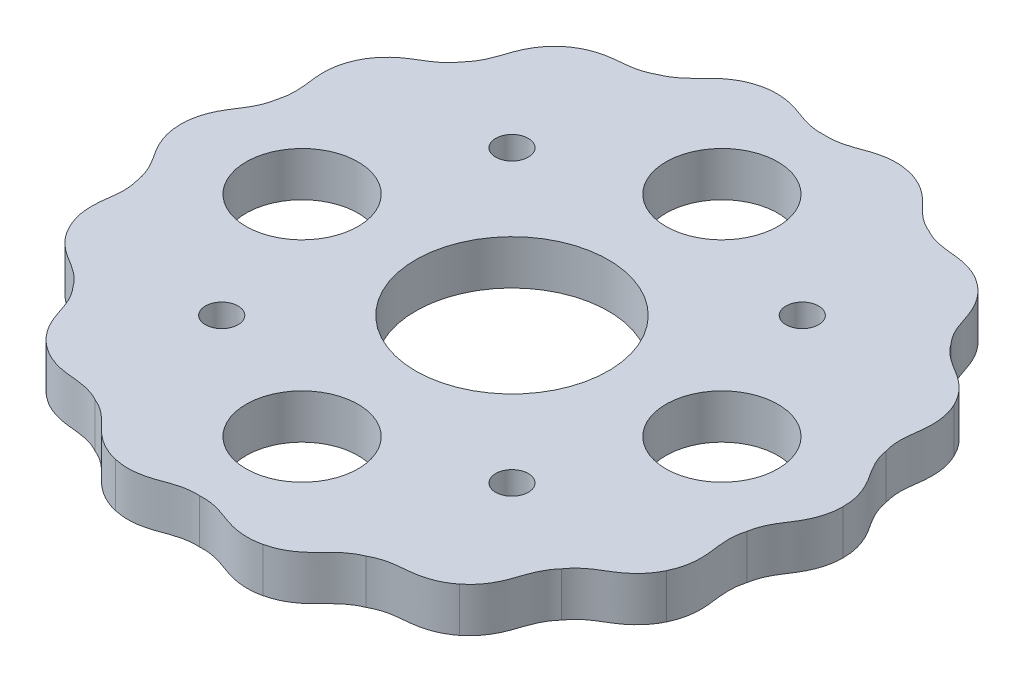
SolidWorks part; units mm, degrees
ref_plane "Front Plane" through (0, 0, 0) normal (0, 0, 1) x (1, 0, 0)
ref_plane "Top Plane" through (0, 0, 0) normal (0, 1, 0) x (1, 0, 0)
ref_plane "Right Plane" through (0, 0, 0) normal (1, 0, 0) x (0, 0, -1)
sketch "Sketch1" plane through (0, 0, 0) normal (0, 1, 0) x (1, 0, 0)
  line L0 (0, 0) -> (37.5, 0) construction
  line L1 (0, 0) -> (37.4807, 1.2019) construction
  line L2 (0, 0) -> (37.423, 2.4026) construction
  line L3 (0, 0) -> (37.3267, 3.6009) construction
  line L4 (0, 0) -> (37.1921, 4.7954) construction
  line L5 (0, 0) -> (37.0193, 5.985) construction
  line L6 (0, 0) -> (36.8085, 7.1684) construction
  line L7 (0, 0) -> (36.5598, 8.3445) construction
  line L8 (0, 0) -> (36.2736, 9.512) construction
  line L9 (0, 0) -> (35.95, 10.6698) construction
  line L10 (0, 0) -> (35.5896, 11.8166) construction
  line L11 (0, 0) -> (35.1926, 12.9512) construction
  line L12 (0, 0) -> (34.7594, 14.0725) construction
  line L13 (0, 0) -> (34.2905, 15.1794) construction
  line L14 (0, 0) -> (33.7863, 16.2706) construction
  line L15 (37.5, 0) -> (38.5, 0) construction
  line L16 (37.4807, 1.2019) -> (38.3521, 1.6927) construction
  line L17 (37.423, 2.4026) -> (37.9413, 3.2578) construction
  line L18 (37.3267, 3.6009) -> (37.3588, 4.6003) construction
  line L19 (37.1921, 4.7954) -> (36.7296, 5.682) construction
  line L20 (37.0193, 5.985) -> (36.1812, 6.5305) construction
  line L21 (36.8085, 7.1684) -> (35.8105, 7.2325) construction
  line L22 (36.5598, 8.3445) -> (35.5849, 8.122) construction
  line L23 (37, 0.0019) -> (37, 0)
  line L24 (33.3367, 16.052) -> (33.3358, 16.0537)
  line L25 (37, -0.0019) -> (37, 0)
  line L26 (33.3367, -16.052) -> (33.3358, -16.0537)
  line L27 (33.335, -16.0554) -> (33.3358, -16.0537)
  line L28 (23.0706, -28.9266) -> (23.0691, -28.9278)
  line L29 (23.0677, -28.9289) -> (23.0691, -28.9278)
  line L30 (8.2351, -36.0719) -> (8.2333, -36.0723)
  line L31 (8.2315, -36.0727) -> (8.2333, -36.0723)
  line L32 (-8.2315, -36.0727) -> (-8.2333, -36.0723)
  line L33 (-8.2351, -36.0719) -> (-8.2333, -36.0723)
  line L34 (-23.0677, -28.9289) -> (-23.0691, -28.9278)
  line L35 (-23.0706, -28.9266) -> (-23.0691, -28.9278)
  line L36 (-33.335, -16.0554) -> (-33.3358, -16.0537)
  line L37 (-33.3367, -16.052) -> (-33.3358, -16.0537)
  line L38 (-37, -0.0019) -> (-37, 0)
  line L39 (-37, 0.0019) -> (-37, 0)
  line L40 (-33.3367, 16.052) -> (-33.3358, 16.0537)
  line L41 (-33.335, 16.0554) -> (-33.3358, 16.0537)
  line L42 (-23.0706, 28.9266) -> (-23.0691, 28.9278)
  line L43 (-23.0677, 28.9289) -> (-23.0691, 28.9278)
  line L44 (-8.2351, 36.0719) -> (-8.2333, 36.0723)
  line L45 (-8.2315, 36.0727) -> (-8.2333, 36.0723)
  line L46 (8.2315, 36.0727) -> (8.2333, 36.0723)
  line L47 (8.2351, 36.0719) -> (8.2333, 36.0723)
  line L48 (23.0677, 28.9289) -> (23.0691, 28.9278)
  line L49 (23.0706, 28.9266) -> (23.0691, 28.9278)
  line L50 (33.335, 16.0554) -> (33.3358, 16.0537)
  line L51 (35.5, 0.0037) -> (35.5, 0)
  line L52 (31.986, 15.3995) -> (31.9844, 15.4029)
  line L53 (35.5, -0.0037) -> (35.5, 0)
  line L54 (31.986, -15.3995) -> (31.9844, -15.4029)
  line L55 (31.9828, -15.4062) -> (31.9844, -15.4029)
  line L56 (22.1368, -27.7527) -> (22.1339, -27.755)
  line L57 (22.131, -27.7573) -> (22.1339, -27.755)
  line L58 (7.9031, -34.6091) -> (7.8995, -34.6099)
  line L59 (7.8959, -34.6108) -> (7.8995, -34.6099)
  line L60 (-7.8959, -34.6108) -> (-7.8995, -34.6099)
  line L61 (-7.9031, -34.6091) -> (-7.8995, -34.6099)
  line L62 (-22.131, -27.7573) -> (-22.1339, -27.755)
  line L63 (-22.1368, -27.7527) -> (-22.1339, -27.755)
  line L64 (-31.9828, -15.4062) -> (-31.9844, -15.4029)
  line L65 (-31.986, -15.3995) -> (-31.9844, -15.4029)
  line L66 (-35.5, -0.0037) -> (-35.5, 0)
  line L67 (-35.5, 0.0037) -> (-35.5, 0)
  line L68 (-31.986, 15.3995) -> (-31.9844, 15.4029)
  line L69 (-31.9828, 15.4062) -> (-31.9844, 15.4029)
  line L70 (-22.1368, 27.7527) -> (-22.1339, 27.755)
  line L71 (-22.131, 27.7573) -> (-22.1339, 27.755)
  line L72 (-7.9031, 34.6091) -> (-7.8995, 34.6099)
  line L73 (-7.8959, 34.6108) -> (-7.8995, 34.6099)
  line L74 (7.8959, 34.6108) -> (7.8995, 34.6099)
  line L75 (7.9031, 34.6091) -> (7.8995, 34.6099)
  line L76 (22.131, 27.7573) -> (22.1339, 27.755)
  line L77 (22.1368, 27.7527) -> (22.1339, 27.755)
  line L78 (31.9828, 15.4062) -> (31.9844, 15.4029)
  circle A0 centre (0, 0) radius 35 construction
  circle A1 centre (37.5, 0) radius 2.5 construction
  circle A2 centre (0, 0) radius 37.5 construction
  spline S0 degree 3 poles (35.5849, 8.122) (35.6266, 7.5364) (36.0345, 6.7125) (36.7836, 5.6218) (37.4152, 4.5501) (38.2239, 2.702) (38.5014, 1.1074) (38.5, 0) knots 0 0 0 0 0.195516 0.310928 0.453873 0.621058 1 1 1 1
  spline S1 degree 3 poles (35.5849, 8.122) (35.3683, 8.6678) (35.3784, 9.5871) (35.5801, 10.8948) (35.6841, 12.1344) (35.611, 14.1503) (35.169, 15.7074) (34.6873, 16.7045) knots 0 0 0 0 0.195516 0.310928 0.453873 0.621058 1 1 1 1
  spline S2 degree 1 poles (34.1119, 7.7858) (33.3367, 16.052) knots 0 0 1 1 construction
  spline S3 degree 1 poles (34.1119, 7.7858) (37, 0.0019) knots 0 0 1 1 construction
  spline S4 degree 3 poles (33.3367, 16.052) (33.6005, 15.5058) (33.9037, 14.6401) (34.1146, 13.4372) (34.174, 12.5211) (34.1413, 11.5771) (34.0239, 10.6392) (33.8823, 9.6155) (33.9055, 8.625) (34.0243, 8.0514) (34.1119, 7.7858) knots 0.015853 0.015853 0.015853 0.015853 0.26189 0.384908 0.507927 0.630945 0.753963 0.876982 0.938491 1 1 1 1
  spline S5 degree 3 poles (34.1119, 7.7858) (34.1483, 7.5085) (34.2901, 6.9402) (34.6989, 6.0377) (35.2706, 5.1769) (35.7834, 4.3828) (36.2224, 3.5464) (36.5664, 2.6953) (36.8983, 1.52) (37.0008, 0.6085) (37, 0.0019) knots 0.015853 0.015853 0.015853 0.015853 0.077362 0.138872 0.26189 0.384908 0.507927 0.630945 0.753963 1 1 1 1
  spline S6 degree 3 poles (37, -0.0019) (37.0008, -0.6085) (36.8983, -1.52) (36.5664, -2.6953) (36.2224, -3.5464) (35.7834, -4.3828) (35.2706, -5.1769) (34.6989, -6.0377) (34.2901, -6.9402) (34.1483, -7.5085) (34.1119, -7.7858) knots 0.015853 0.015853 0.015853 0.015853 0.26189 0.384908 0.507927 0.630945 0.753963 0.876982 0.938491 1 1 1 1
  spline S7 degree 3 poles (34.1119, -7.7858) (34.0243, -8.0514) (33.9055, -8.625) (33.8823, -9.6155) (34.0239, -10.6392) (34.1413, -11.5771) (34.174, -12.5211) (34.1146, -13.4372) (33.9037, -14.6401) (33.6005, -15.5058) (33.3367, -16.052) knots 0.015853 0.015853 0.015853 0.015853 0.077362 0.138872 0.26189 0.384908 0.507927 0.630945 0.753963 1 1 1 1
  spline S8 degree 3 poles (33.335, -16.0554) (33.0725, -16.6022) (32.5847, -17.3791) (31.7758, -18.2939) (31.0965, -18.9115) (30.3381, -19.4746) (29.5316, -19.9675) (28.6429, -20.4951) (27.8831, -21.1308) (27.5087, -21.5813) (27.3556, -21.8154) knots 0.015853 0.015853 0.015853 0.015853 0.26189 0.384908 0.507927 0.630945 0.753963 0.876982 0.938491 1 1 1 1
  spline S9 degree 3 poles (27.3556, -21.8154) (27.1615, -22.0167) (26.8056, -22.4819) (26.3549, -23.3642) (26.0383, -24.348) (25.7371, -25.2439) (25.357, -26.1087) (24.906, -26.9083) (24.1941, -27.9005) (23.5453, -28.549) (23.0706, -28.9266) knots 0.015853 0.015853 0.015853 0.015853 0.077362 0.138872 0.26189 0.384908 0.507927 0.630945 0.753963 1 1 1 1
  spline S10 degree 3 poles (23.0677, -28.9289) (22.5939, -29.3077) (21.8173, -29.796) (20.6915, -30.2693) (19.8116, -30.531) (18.884, -30.7092) (17.9435, -30.8034) (16.9139, -30.8931) (15.9535, -31.1362) (15.4207, -31.3797) (15.1812, -31.5241) knots 0.015853 0.015853 0.015853 0.015853 0.26189 0.384908 0.507927 0.630945 0.753963 0.876982 0.938491 1 1 1 1
  spline S11 degree 3 poles (15.1812, -31.5241) (14.919, -31.6213) (14.3964, -31.886) (13.6076, -32.4854) (12.8955, -33.2344) (12.2354, -33.9109) (11.5177, -34.5251) (10.7645, -35.0499) (9.6926, -35.6349) (8.8266, -35.9377) (8.2351, -36.0719) knots 0.015853 0.015853 0.015853 0.015853 0.077362 0.138872 0.26189 0.384908 0.507927 0.630945 0.753963 1 1 1 1
  spline S12 degree 3 poles (8.2315, -36.0727) (7.6402, -36.2085) (6.7287, -36.3114) (5.5091, -36.2494) (4.6028, -36.1034) (3.6897, -35.8614) (2.8014, -35.5383) (1.8349, -35.1724) (0.8641, -34.9747) (0.2785, -34.9629) (0, -34.9891) knots 0.015853 0.015853 0.015853 0.015853 0.26189 0.384908 0.507927 0.630945 0.753963 0.876982 0.938491 1 1 1 1
  spline S13 degree 3 poles (0, -34.9891) (-0.2785, -34.9629) (-0.8641, -34.9747) (-1.8349, -35.1724) (-2.8014, -35.5383) (-3.6897, -35.8614) (-4.6028, -36.1034) (-5.5091, -36.2494) (-6.7287, -36.3114) (-7.6402, -36.2085) (-8.2315, -36.0727) knots 0.015853 0.015853 0.015853 0.015853 0.077362 0.138872 0.26189 0.384908 0.507927 0.630945 0.753963 1 1 1 1
  spline S14 degree 3 poles (-8.2351, -36.0719) (-8.8266, -35.9377) (-9.6926, -35.6349) (-10.7645, -35.0499) (-11.5177, -34.5251) (-12.2354, -33.9109) (-12.8955, -33.2344) (-13.6076, -32.4854) (-14.3964, -31.886) (-14.919, -31.6213) (-15.1812, -31.5241) knots 0.015853 0.015853 0.015853 0.015853 0.26189 0.384908 0.507927 0.630945 0.753963 0.876982 0.938491 1 1 1 1
  spline S15 degree 3 poles (-15.1812, -31.5241) (-15.4207, -31.3797) (-15.9535, -31.1362) (-16.9139, -30.8931) (-17.9435, -30.8034) (-18.884, -30.7092) (-19.8116, -30.531) (-20.6915, -30.2693) (-21.8173, -29.796) (-22.5939, -29.3077) (-23.0677, -28.9289) knots 0.015853 0.015853 0.015853 0.015853 0.077362 0.138872 0.26189 0.384908 0.507927 0.630945 0.753963 1 1 1 1
  spline S16 degree 3 poles (-23.0706, -28.9266) (-23.5453, -28.549) (-24.1941, -27.9005) (-24.906, -26.9083) (-25.357, -26.1087) (-25.7371, -25.2439) (-26.0383, -24.348) (-26.3549, -23.3642) (-26.8056, -22.4819) (-27.1615, -22.0167) (-27.3556, -21.8154) knots 0.015853 0.015853 0.015853 0.015853 0.26189 0.384908 0.507927 0.630945 0.753963 0.876982 0.938491 1 1 1 1
  spline S17 degree 3 poles (-27.3556, -21.8154) (-27.5087, -21.5813) (-27.8831, -21.1308) (-28.6429, -20.4951) (-29.5316, -19.9675) (-30.3381, -19.4746) (-31.0965, -18.9115) (-31.7758, -18.2939) (-32.5847, -17.3791) (-33.0725, -16.6022) (-33.335, -16.0554) knots 0.015853 0.015853 0.015853 0.015853 0.077362 0.138872 0.26189 0.384908 0.507927 0.630945 0.753963 1 1 1 1
  spline S18 degree 3 poles (-33.3367, -16.052) (-33.6005, -15.5058) (-33.9037, -14.6401) (-34.1146, -13.4372) (-34.174, -12.5211) (-34.1413, -11.5771) (-34.0239, -10.6392) (-33.8823, -9.6155) (-33.9055, -8.625) (-34.0243, -8.0514) (-34.1119, -7.7858) knots 0.015853 0.015853 0.015853 0.015853 0.26189 0.384908 0.507927 0.630945 0.753963 0.876982 0.938491 1 1 1 1
  spline S19 degree 3 poles (-34.1119, -7.7858) (-34.1483, -7.5085) (-34.2901, -6.9402) (-34.6989, -6.0377) (-35.2706, -5.1769) (-35.7834, -4.3828) (-36.2224, -3.5464) (-36.5664, -2.6953) (-36.8983, -1.52) (-37.0008, -0.6085) (-37, -0.0019) knots 0.015853 0.015853 0.015853 0.015853 0.077362 0.138872 0.26189 0.384908 0.507927 0.630945 0.753963 1 1 1 1
  spline S20 degree 3 poles (-37, 0.0019) (-37.0008, 0.6085) (-36.8983, 1.52) (-36.5664, 2.6953) (-36.2224, 3.5464) (-35.7834, 4.3828) (-35.2706, 5.1769) (-34.6989, 6.0377) (-34.2901, 6.9402) (-34.1483, 7.5085) (-34.1119, 7.7858) knots 0.015853 0.015853 0.015853 0.015853 0.26189 0.384908 0.507927 0.630945 0.753963 0.876982 0.938491 1 1 1 1
  spline S21 degree 3 poles (-34.1119, 7.7858) (-34.0243, 8.0514) (-33.9055, 8.625) (-33.8823, 9.6155) (-34.0239, 10.6392) (-34.1413, 11.5771) (-34.174, 12.5211) (-34.1146, 13.4372) (-33.9037, 14.6401) (-33.6005, 15.5058) (-33.3367, 16.052) knots 0.015853 0.015853 0.015853 0.015853 0.077362 0.138872 0.26189 0.384908 0.507927 0.630945 0.753963 1 1 1 1
  spline S22 degree 3 poles (-33.335, 16.0554) (-33.0725, 16.6022) (-32.5847, 17.3791) (-31.7758, 18.2939) (-31.0965, 18.9115) (-30.3381, 19.4746) (-29.5316, 19.9675) (-28.6429, 20.4951) (-27.8831, 21.1308) (-27.5087, 21.5813) (-27.3556, 21.8154) knots 0.015853 0.015853 0.015853 0.015853 0.26189 0.384908 0.507927 0.630945 0.753963 0.876982 0.938491 1 1 1 1
  spline S23 degree 3 poles (-27.3556, 21.8154) (-27.1615, 22.0167) (-26.8056, 22.4819) (-26.3549, 23.3642) (-26.0383, 24.348) (-25.7371, 25.2439) (-25.357, 26.1087) (-24.906, 26.9083) (-24.1941, 27.9005) (-23.5453, 28.549) (-23.0706, 28.9266) knots 0.015853 0.015853 0.015853 0.015853 0.077362 0.138872 0.26189 0.384908 0.507927 0.630945 0.753963 1 1 1 1
  spline S24 degree 3 poles (-23.0677, 28.9289) (-22.5939, 29.3077) (-21.8173, 29.796) (-20.6915, 30.2693) (-19.8116, 30.531) (-18.884, 30.7092) (-17.9435, 30.8034) (-16.9139, 30.8931) (-15.9535, 31.1362) (-15.4207, 31.3797) (-15.1812, 31.5241) knots 0.015853 0.015853 0.015853 0.015853 0.26189 0.384908 0.507927 0.630945 0.753963 0.876982 0.938491 1 1 1 1
  spline S25 degree 3 poles (-15.1812, 31.5241) (-14.919, 31.6213) (-14.3964, 31.886) (-13.6076, 32.4854) (-12.8955, 33.2344) (-12.2354, 33.9109) (-11.5177, 34.5251) (-10.7645, 35.0499) (-9.6926, 35.6349) (-8.8266, 35.9377) (-8.2351, 36.0719) knots 0.015853 0.015853 0.015853 0.015853 0.077362 0.138872 0.26189 0.384908 0.507927 0.630945 0.753963 1 1 1 1
  spline S26 degree 3 poles (-8.2315, 36.0727) (-7.6402, 36.2085) (-6.7287, 36.3114) (-5.5091, 36.2494) (-4.6028, 36.1034) (-3.6897, 35.8614) (-2.8014, 35.5383) (-1.8349, 35.1724) (-0.8641, 34.9747) (-0.2785, 34.9629) (0, 34.9891) knots 0.015853 0.015853 0.015853 0.015853 0.26189 0.384908 0.507927 0.630945 0.753963 0.876982 0.938491 1 1 1 1
  spline S27 degree 3 poles (0, 34.9891) (0.2785, 34.9629) (0.8641, 34.9747) (1.8349, 35.1724) (2.8014, 35.5383) (3.6897, 35.8614) (4.6028, 36.1034) (5.5091, 36.2494) (6.7287, 36.3114) (7.6402, 36.2085) (8.2315, 36.0727) knots 0.015853 0.015853 0.015853 0.015853 0.077362 0.138872 0.26189 0.384908 0.507927 0.630945 0.753963 1 1 1 1
  spline S28 degree 3 poles (8.2351, 36.0719) (8.8266, 35.9377) (9.6926, 35.6349) (10.7645, 35.0499) (11.5177, 34.5251) (12.2354, 33.9109) (12.8955, 33.2344) (13.6076, 32.4854) (14.3964, 31.886) (14.919, 31.6213) (15.1812, 31.5241) knots 0.015853 0.015853 0.015853 0.015853 0.26189 0.384908 0.507927 0.630945 0.753963 0.876982 0.938491 1 1 1 1
  spline S29 degree 3 poles (15.1812, 31.5241) (15.4207, 31.3797) (15.9535, 31.1362) (16.9139, 30.8931) (17.9435, 30.8034) (18.884, 30.7092) (19.8116, 30.531) (20.6915, 30.2693) (21.8173, 29.796) (22.5939, 29.3077) (23.0677, 28.9289) knots 0.015853 0.015853 0.015853 0.015853 0.077362 0.138872 0.26189 0.384908 0.507927 0.630945 0.753963 1 1 1 1
  spline S30 degree 3 poles (23.0706, 28.9266) (23.5453, 28.549) (24.1941, 27.9005) (24.906, 26.9083) (25.357, 26.1087) (25.7371, 25.2439) (26.0383, 24.348) (26.3549, 23.3642) (26.8056, 22.4819) (27.1615, 22.0167) (27.3556, 21.8154) knots 0.015853 0.015853 0.015853 0.015853 0.26189 0.384908 0.507927 0.630945 0.753963 0.876982 0.938491 1 1 1 1
  spline S31 degree 3 poles (27.3556, 21.8154) (27.5087, 21.5813) (27.8831, 21.1308) (28.6429, 20.4951) (29.5316, 19.9675) (30.3381, 19.4746) (31.0965, 18.9115) (31.7758, 18.2939) (32.5847, 17.3791) (33.0725, 16.6022) (33.335, 16.0554) knots 0.015853 0.015853 0.015853 0.015853 0.077362 0.138872 0.26189 0.384908 0.507927 0.630945 0.753963 1 1 1 1
  spline S32 degree 1 poles (32.6448, 7.451) (35.5, 0.0037) knots 0 0 1 1 construction
  spline S33 degree 1 poles (32.6448, 7.451) (31.986, 15.3995) knots 0 0 1 1 construction
  spline S34 degree 3 poles (35.5, 0.0037) (35.5006, 0.4959) (35.4183, 1.2336) (35.1496, 2.1927) (34.8707, 2.8896) (34.4997, 3.6015) (34.1394, 4.1652) (33.6939, 4.8394) (33.3068, 5.4873) (32.9751, 6.1975) (32.758, 6.8733) (32.6748, 7.2607) (32.6448, 7.451) knots 0.023011 0.023011 0.023011 0.023011 0.267258 0.389382 0.511505 0.633629 0.755753 0.816814 0.877876 0.938938 0.969469 1 1 1 1
  spline S35 degree 3 poles (32.6448, 7.451) (32.5893, 7.6354) (32.4961, 8.0206) (32.3985, 8.7236) (32.3893, 9.5074) (32.4569, 10.2591) (32.5657, 11.0598) (32.6458, 11.724) (32.6712, 12.5264) (32.6201, 13.2752) (32.446, 14.256) (32.2001, 14.9563) (31.986, 15.3995) knots 0.023011 0.023011 0.023011 0.023011 0.053542 0.084072 0.145134 0.206196 0.267258 0.389382 0.511505 0.633629 0.755753 1 1 1 1
  spline S36 degree 3 poles (32.6448, -7.451) (32.6748, -7.2607) (32.758, -6.8733) (32.9751, -6.1975) (33.3068, -5.4873) (33.6939, -4.8394) (34.1394, -4.1652) (34.4997, -3.6015) (34.8707, -2.8896) (35.1496, -2.1927) (35.4183, -1.2336) (35.5006, -0.4959) (35.5, -0.0037) knots 0.023011 0.023011 0.023011 0.023011 0.053542 0.084072 0.145134 0.206196 0.267258 0.389382 0.511505 0.633629 0.755753 1 1 1 1
  spline S37 degree 3 poles (31.986, -15.3995) (32.2001, -14.9563) (32.446, -14.256) (32.6201, -13.2752) (32.6712, -12.5264) (32.6458, -11.724) (32.5657, -11.0598) (32.4569, -10.2591) (32.3893, -9.5074) (32.3985, -8.7236) (32.4961, -8.0206) (32.5893, -7.6354) (32.6448, -7.451) knots 0.023011 0.023011 0.023011 0.023011 0.267258 0.389382 0.511505 0.633629 0.755753 0.816814 0.877876 0.938938 0.969469 1 1 1 1
  spline S38 degree 3 poles (26.1791, -20.8771) (26.2887, -20.7187) (26.5317, -20.4057) (27.0205, -19.8911) (27.6275, -19.3952) (28.2574, -18.9793) (28.9513, -18.5652) (29.5206, -18.2137) (30.1637, -17.7333) (30.7173, -17.2264) (31.3755, -16.4789) (31.7698, -15.8499) (31.9828, -15.4062) knots 0.023011 0.023011 0.023011 0.023011 0.053542 0.084072 0.145134 0.206196 0.267258 0.389382 0.511505 0.633629 0.755753 1 1 1 1
  spline S39 degree 3 poles (22.1368, -27.7527) (22.522, -27.4463) (23.0474, -26.922) (23.6297, -26.1139) (24.0007, -25.4614) (24.326, -24.7275) (24.542, -24.0943) (24.7914, -23.3257) (25.0566, -22.619) (25.405, -21.9169) (25.798, -21.3258) (26.0491, -21.0192) (26.1791, -20.8771) knots 0.023011 0.023011 0.023011 0.023011 0.267258 0.389382 0.511505 0.633629 0.755753 0.816814 0.877876 0.938938 0.969469 1 1 1 1
  spline S40 degree 3 poles (14.5283, -30.1683) (14.6957, -30.0732) (15.0505, -29.8966) (15.7143, -29.645) (16.4763, -29.4616) (17.2242, -29.3602) (18.0291, -29.2882) (18.6945, -29.2185) (19.4823, -29.0647) (20.201, -28.8482) (21.1184, -28.4603) (21.7465, -28.0647) (22.131, -27.7573) knots 0.023011 0.023011 0.023011 0.023011 0.053542 0.084072 0.145134 0.206196 0.267258 0.389382 0.511505 0.633629 0.755753 1 1 1 1
  spline S41 degree 3 poles (7.9031, -34.6091) (8.3831, -34.5002) (9.084, -34.2557) (9.9593, -33.7804) (10.5766, -33.3534) (11.1881, -32.8334) (11.6575, -32.3566) (12.2156, -31.7723) (12.7612, -31.2507) (13.3797, -30.7693) (13.9903, -30.4072) (14.3495, -30.2399) (14.5283, -30.1683) knots 0.023011 0.023011 0.023011 0.023011 0.267258 0.389382 0.511505 0.633629 0.755753 0.816814 0.877876 0.938938 0.969469 1 1 1 1
  spline S42 degree 3 poles (0, -33.4843) (0.1922, -33.4712) (0.5884, -33.4661) (1.2956, -33.5274) (2.0617, -33.6928) (2.7796, -33.926) (3.536, -34.2103) (4.1657, -34.4362) (4.9423, -34.6394) (5.6838, -34.7562) (6.6786, -34.8048) (7.4161, -34.7209) (7.8959, -34.6108) knots 0.023011 0.023011 0.023011 0.023011 0.053542 0.084072 0.145134 0.206196 0.267258 0.389382 0.511505 0.633629 0.755753 1 1 1 1
  spline S43 degree 3 poles (-7.8959, -34.6108) (-7.4161, -34.7209) (-6.6786, -34.8048) (-5.6838, -34.7562) (-4.9423, -34.6394) (-4.1657, -34.4362) (-3.536, -34.2103) (-2.7796, -33.926) (-2.0617, -33.6928) (-1.2956, -33.5274) (-0.5884, -33.4661) (-0.1922, -33.4712) (0, -33.4843) knots 0.023011 0.023011 0.023011 0.023011 0.267258 0.389382 0.511505 0.633629 0.755753 0.816814 0.877876 0.938938 0.969469 1 1 1 1
  spline S44 degree 3 poles (-14.5283, -30.1683) (-14.3495, -30.2399) (-13.9903, -30.4072) (-13.3797, -30.7693) (-12.7612, -31.2507) (-12.2156, -31.7723) (-11.6575, -32.3566) (-11.1881, -32.8334) (-10.5766, -33.3534) (-9.9593, -33.7804) (-9.084, -34.2557) (-8.3831, -34.5002) (-7.9031, -34.6091) knots 0.023011 0.023011 0.023011 0.023011 0.053542 0.084072 0.145134 0.206196 0.267258 0.389382 0.511505 0.633629 0.755753 1 1 1 1
  spline S45 degree 3 poles (-22.131, -27.7573) (-21.7465, -28.0647) (-21.1184, -28.4603) (-20.201, -28.8482) (-19.4823, -29.0647) (-18.6945, -29.2185) (-18.0291, -29.2882) (-17.2242, -29.3602) (-16.4763, -29.4616) (-15.7143, -29.645) (-15.0505, -29.8966) (-14.6957, -30.0732) (-14.5283, -30.1683) knots 0.023011 0.023011 0.023011 0.023011 0.267258 0.389382 0.511505 0.633629 0.755753 0.816814 0.877876 0.938938 0.969469 1 1 1 1
  spline S46 degree 3 poles (-26.1791, -20.8771) (-26.0491, -21.0192) (-25.798, -21.3258) (-25.405, -21.9169) (-25.0566, -22.619) (-24.7914, -23.3257) (-24.542, -24.0943) (-24.326, -24.7275) (-24.0007, -25.4614) (-23.6297, -26.1139) (-23.0474, -26.922) (-22.522, -27.4463) (-22.1368, -27.7527) knots 0.023011 0.023011 0.023011 0.023011 0.053542 0.084072 0.145134 0.206196 0.267258 0.389382 0.511505 0.633629 0.755753 1 1 1 1
  spline S47 degree 3 poles (-31.9828, -15.4062) (-31.7698, -15.8499) (-31.3755, -16.4789) (-30.7173, -17.2264) (-30.1637, -17.7333) (-29.5206, -18.2137) (-28.9513, -18.5652) (-28.2574, -18.9793) (-27.6275, -19.3952) (-27.0205, -19.8911) (-26.5317, -20.4057) (-26.2887, -20.7187) (-26.1791, -20.8771) knots 0.023011 0.023011 0.023011 0.023011 0.267258 0.389382 0.511505 0.633629 0.755753 0.816814 0.877876 0.938938 0.969469 1 1 1 1
  spline S48 degree 3 poles (-32.6448, -7.451) (-32.5893, -7.6354) (-32.4961, -8.0206) (-32.3985, -8.7236) (-32.3893, -9.5074) (-32.4569, -10.2591) (-32.5657, -11.0598) (-32.6458, -11.724) (-32.6712, -12.5264) (-32.6201, -13.2752) (-32.446, -14.256) (-32.2001, -14.9563) (-31.986, -15.3995) knots 0.023011 0.023011 0.023011 0.023011 0.053542 0.084072 0.145134 0.206196 0.267258 0.389382 0.511505 0.633629 0.755753 1 1 1 1
  spline S49 degree 3 poles (-35.5, -0.0037) (-35.5006, -0.4959) (-35.4183, -1.2336) (-35.1496, -2.1927) (-34.8707, -2.8896) (-34.4997, -3.6015) (-34.1394, -4.1652) (-33.6939, -4.8394) (-33.3068, -5.4873) (-32.9751, -6.1975) (-32.758, -6.8733) (-32.6748, -7.2607) (-32.6448, -7.451) knots 0.023011 0.023011 0.023011 0.023011 0.267258 0.389382 0.511505 0.633629 0.755753 0.816814 0.877876 0.938938 0.969469 1 1 1 1
  spline S50 degree 3 poles (-32.6448, 7.451) (-32.6748, 7.2607) (-32.758, 6.8733) (-32.9751, 6.1975) (-33.3068, 5.4873) (-33.6939, 4.8394) (-34.1394, 4.1652) (-34.4997, 3.6015) (-34.8707, 2.8896) (-35.1496, 2.1927) (-35.4183, 1.2336) (-35.5006, 0.4959) (-35.5, 0.0037) knots 0.023011 0.023011 0.023011 0.023011 0.053542 0.084072 0.145134 0.206196 0.267258 0.389382 0.511505 0.633629 0.755753 1 1 1 1
  spline S51 degree 3 poles (-31.986, 15.3995) (-32.2001, 14.9563) (-32.446, 14.256) (-32.6201, 13.2752) (-32.6712, 12.5264) (-32.6458, 11.724) (-32.5657, 11.0598) (-32.4569, 10.2591) (-32.3893, 9.5074) (-32.3985, 8.7236) (-32.4961, 8.0206) (-32.5893, 7.6354) (-32.6448, 7.451) knots 0.023011 0.023011 0.023011 0.023011 0.267258 0.389382 0.511505 0.633629 0.755753 0.816814 0.877876 0.938938 0.969469 1 1 1 1
  spline S52 degree 3 poles (-26.1791, 20.8771) (-26.2887, 20.7187) (-26.5317, 20.4057) (-27.0205, 19.8911) (-27.6275, 19.3952) (-28.2574, 18.9793) (-28.9513, 18.5652) (-29.5206, 18.2137) (-30.1637, 17.7333) (-30.7173, 17.2264) (-31.3755, 16.4789) (-31.7698, 15.8499) (-31.9828, 15.4062) knots 0.023011 0.023011 0.023011 0.023011 0.053542 0.084072 0.145134 0.206196 0.267258 0.389382 0.511505 0.633629 0.755753 1 1 1 1
  spline S53 degree 3 poles (-22.1368, 27.7527) (-22.522, 27.4463) (-23.0474, 26.922) (-23.6297, 26.1139) (-24.0007, 25.4614) (-24.326, 24.7275) (-24.542, 24.0943) (-24.7914, 23.3257) (-25.0566, 22.619) (-25.405, 21.9169) (-25.798, 21.3258) (-26.0491, 21.0192) (-26.1791, 20.8771) knots 0.023011 0.023011 0.023011 0.023011 0.267258 0.389382 0.511505 0.633629 0.755753 0.816814 0.877876 0.938938 0.969469 1 1 1 1
  spline S54 degree 3 poles (-14.5283, 30.1683) (-14.6957, 30.0732) (-15.0505, 29.8966) (-15.7143, 29.645) (-16.4763, 29.4616) (-17.2242, 29.3602) (-18.0291, 29.2882) (-18.6945, 29.2185) (-19.4823, 29.0647) (-20.201, 28.8482) (-21.1184, 28.4603) (-21.7465, 28.0647) (-22.131, 27.7573) knots 0.023011 0.023011 0.023011 0.023011 0.053542 0.084072 0.145134 0.206196 0.267258 0.389382 0.511505 0.633629 0.755753 1 1 1 1
  spline S55 degree 3 poles (-7.9031, 34.6091) (-8.3831, 34.5002) (-9.084, 34.2557) (-9.9593, 33.7804) (-10.5766, 33.3534) (-11.1881, 32.8334) (-11.6575, 32.3566) (-12.2156, 31.7723) (-12.7612, 31.2507) (-13.3797, 30.7693) (-13.9903, 30.4072) (-14.3495, 30.2399) (-14.5283, 30.1683) knots 0.023011 0.023011 0.023011 0.023011 0.267258 0.389382 0.511505 0.633629 0.755753 0.816814 0.877876 0.938938 0.969469 1 1 1 1
  spline S56 degree 3 poles (0, 33.4843) (-0.1922, 33.4712) (-0.5884, 33.4661) (-1.2956, 33.5274) (-2.0617, 33.6928) (-2.7796, 33.926) (-3.536, 34.2103) (-4.1657, 34.4362) (-4.9423, 34.6394) (-5.6838, 34.7562) (-6.6786, 34.8048) (-7.4161, 34.7209) (-7.8959, 34.6108) knots 0.023011 0.023011 0.023011 0.023011 0.053542 0.084072 0.145134 0.206196 0.267258 0.389382 0.511505 0.633629 0.755753 1 1 1 1
  spline S57 degree 3 poles (7.8959, 34.6108) (7.4161, 34.7209) (6.6786, 34.8048) (5.6838, 34.7562) (4.9423, 34.6394) (4.1657, 34.4362) (3.536, 34.2103) (2.7796, 33.926) (2.0617, 33.6928) (1.2956, 33.5274) (0.5884, 33.4661) (0.1922, 33.4712) (0, 33.4843) knots 0.023011 0.023011 0.023011 0.023011 0.267258 0.389382 0.511505 0.633629 0.755753 0.816814 0.877876 0.938938 0.969469 1 1 1 1
  spline S58 degree 3 poles (14.5283, 30.1683) (14.3495, 30.2399) (13.9903, 30.4072) (13.3797, 30.7693) (12.7612, 31.2507) (12.2156, 31.7723) (11.6575, 32.3566) (11.1881, 32.8334) (10.5766, 33.3534) (9.9593, 33.7804) (9.084, 34.2557) (8.3831, 34.5002) (7.9031, 34.6091) knots 0.023011 0.023011 0.023011 0.023011 0.053542 0.084072 0.145134 0.206196 0.267258 0.389382 0.511505 0.633629 0.755753 1 1 1 1
  spline S59 degree 3 poles (22.131, 27.7573) (21.7465, 28.0647) (21.1184, 28.4603) (20.201, 28.8482) (19.4823, 29.0647) (18.6945, 29.2185) (18.0291, 29.2882) (17.2242, 29.3602) (16.4763, 29.4616) (15.7143, 29.645) (15.0505, 29.8966) (14.6957, 30.0732) (14.5283, 30.1683) knots 0.023011 0.023011 0.023011 0.023011 0.267258 0.389382 0.511505 0.633629 0.755753 0.816814 0.877876 0.938938 0.969469 1 1 1 1
  spline S60 degree 3 poles (26.1791, 20.8771) (26.0491, 21.0192) (25.798, 21.3258) (25.405, 21.9169) (25.0566, 22.619) (24.7914, 23.3257) (24.542, 24.0943) (24.326, 24.7275) (24.0007, 25.4614) (23.6297, 26.1139) (23.0474, 26.922) (22.522, 27.4463) (22.1368, 27.7527) knots 0.023011 0.023011 0.023011 0.023011 0.053542 0.084072 0.145134 0.206196 0.267258 0.389382 0.511505 0.633629 0.755753 1 1 1 1
  spline S61 degree 3 poles (31.9828, 15.4062) (31.7698, 15.8499) (31.3755, 16.4789) (30.7173, 17.2264) (30.1637, 17.7333) (29.5206, 18.2137) (28.9513, 18.5652) (28.2574, 18.9793) (27.6275, 19.3952) (27.0205, 19.8911) (26.5317, 20.4057) (26.2887, 20.7187) (26.1791, 20.8771) knots 0.023011 0.023011 0.023011 0.023011 0.267258 0.389382 0.511505 0.633629 0.755753 0.816814 0.877876 0.938938 0.969469 1 1 1 1
  point P25 (0, 0)
  point P117 (0, 0)
  point P174 (0, 0)
  dimension "D1" = 70
  dimension "D2" = 5
  dimension "D4" = 25.714
  dimension "D5" = 1
  dimension "D7" = 180
  dimension "D8" = 207.551
  dimension "D6" = 1
  dimension "D9" = 1
  dimension "D10" = 235.102
  dimension "D11" = 1
  dimension "D12" = 1
  dimension "D13" = 1
  dimension "D14" = 1
  dimension "D15" = 1
  dimension "D16" = 262.653
  dimension "D17" = 290.204
  dimension "D18" = 317.755
  dimension "D19" = 345.306
  dimension "D20" = 1.5
  dimension "D22" = 3
  dimension "D3" = 15
  dimension "D21" = 14
  dimension "D23" = 14
extrude "Boss-Extrude3" add sketch "Sketch1" along normal blind 4.7625 contours L51 L53 S36 S37 L54 L55 S38 S39 L56 L57 S40 S41 L58 L59 S42 S43 L60 L61 S44 S45 L62 L63 S46 S47 L64 L65 S48 S49 L66 L67 S50 S51 L68 L69 S52 S53 L70 L71 S54 S55 L72 L73 S56 S57 L74 L75 S58 S59 L76 L77 S60 S61 L78 L52 S35 S34
sketch "Sketch2" plane through (0, 4.7625, 0) normal (0, 1, 0) x (1, 0, 0)
  line L0 (0, 0) -> (22.5, 0) construction
  line L1 (0, 0) -> (15.5563, 15.5563) construction
  circle A0 centre (0, 0) radius 10.3281
  circle A1 centre (22.5, 0) radius 6
  circle A6 centre (15.5563, 15.5563) radius 1.75
  circle A7 centre (0, -22.5) radius 6
  circle A8 centre (15.5563, -15.5563) radius 1.75
  circle A9 centre (-22.5, 0) radius 6
  circle A10 centre (-15.5563, -15.5563) radius 1.75
  circle A11 centre (0, 22.5) radius 6
  circle A12 centre (-15.5563, 15.5563) radius 1.75
  point P16 (0, 0)
  point P21 (0, 0)
  point P24 (0, 0)
  dimension "D3" = 12
  dimension "D1" = 20.6562
  dimension "D6" = 3.5
  dimension "D2" = 22.5
  dimension "D4" = 45
  dimension "D5" = 22
  dimension "D7" = 4
extrude "Cut-Extrude1" cut sketch "Sketch2" against normal blind 4.7625 contours A7 | A0 | A0 | A0 | L0 A0 | A0 L0 | A1 | A9 | A11 region at (0, 4.7625, 0) region at (22.5, 4.7625, 0) region at (0, 4.7625, 22.5) region at (-22.5, 4.7625, 0) region at (0, 4.7625, -22.5)
extrude "Cut-Extrude2" cut sketch "Sketch2<4>" against normal blind 2.625 contours A12 | A10 | A8 | A6 region at (15.5563, 4.7625, -15.5563) region at (15.5563, 4.7625, 15.5563) region at (-15.5563, 4.7625, 15.5563) region at (-15.5563, 4.7625, -15.5563)
sketch "Sketch2<4>" plane through (0, 4.7625, 0) normal (0, 1, 0) x (1, 0, 0) same geometry as "Sketch2"
sketch "Sketch3" plane through (0, 4.7625, 0) normal (0, 1, 0) x (1, 0, 0)
  circle A0 centre (0, 0) radius 11.25
  dimension "D1" = 22.5
extrude "Cut-Extrude4" [suppressed] cut sketch "Sketch3" along normal blind 0.8 from surface starting at face at (0, 0, 28.5)
equation "\"D5@Sketch1\" = \"eccentricity\""
equation "\"D6@Sketch1\" = \"eccentricity\""
equation "\"D9@Sketch1\" = \"eccentricity\""
equation "\"D11@Sketch1\" = \"eccentricity\""
equation "\"D12@Sketch1\" = \"eccentricity\""
equation "\"D14@Sketch1\" = \"eccentricity\""
equation "\"D13@Sketch1\" = \"eccentricity\""
equation "\"D15@Sketch1\"= \"eccentricity\""
equation "\"D1@Sketch2\"=\"largeBearOD\"-\"largeBearOTight\""
equation "\"D1@Cut-Extrude2\"=\"ballBearDiam\" * 0.75"
equation "\"D1@Boss-Extrude3\"=\"sheetThickness\""
equation "\"smallBearOD\"= 14.8mm"
equation "\"smallBearID\" = 10mm"
equation "\"smallBearOTight\"= 0mm'calibrate - hold onto bottom of gearbox"
equation "\"smallBearOLoose\"= 0mm'calibrate - able to take off topHat"
equation "\"smallBearITight\" = 0mm'hold onto "
equation "\"pinCircleDiam\"= 75mm"
equation "\"pinDiam\"= 6mm"
equation "\"sheetThickness\"= 0.1875in"
equation "\"D6@Sketch2\"=\"ballBearDiam\""
equation "\"largeBearOD\"= 21mm"
equation "\"largeBearID\" = 15mm"
equation "\"largeBearOTight\"= 0.34375mm'calibrate - hold onto gears"
equation "\"largeBearITight\"= 0mm'calibrate - hold onto eccentric nut"
equation "\"ballBearDiam\"= 3.5mm"
equation "\"thrustBearingThickness\"= 5mm'measure this irl and change"
equation "\"thrustBearingID\"= 0mm'measure this irl and change"
equation "\"thrustBearingOD\"= 0mm'measure this irl and change"
equation "\"eccentricity\" = 1mm"
equation "\"D1@Cut-Extrude1\"=\"sheetThickness\""
